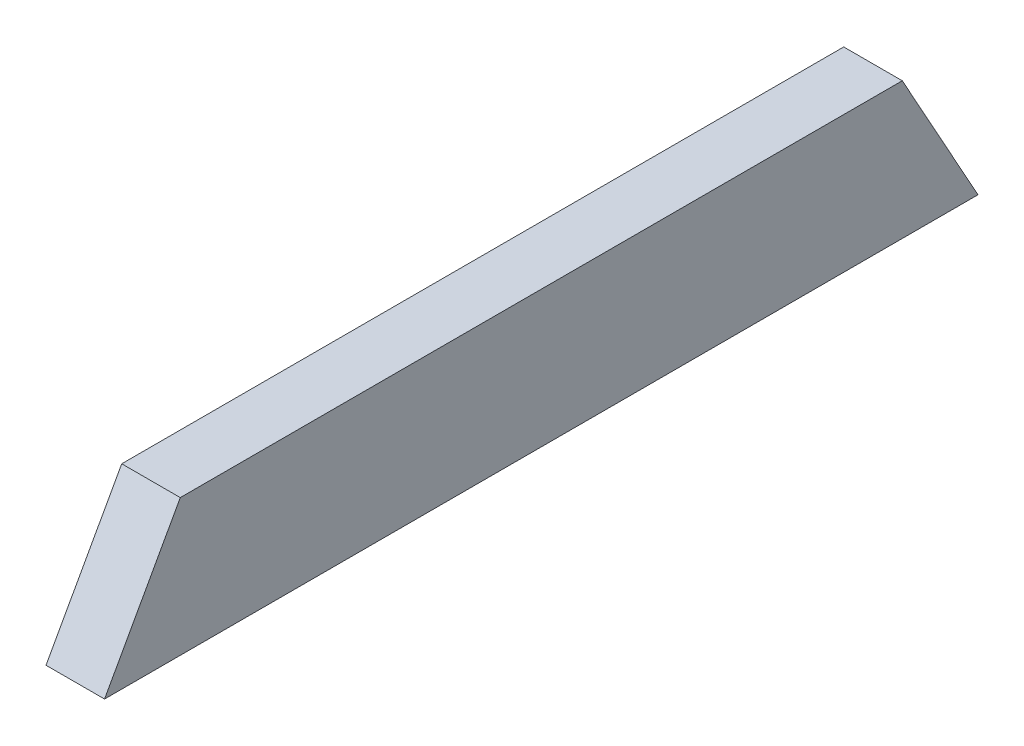
SolidWorks part; units mm, degrees
ref_plane "Front Plane" through (0, 0, 0) normal (0, 0, 1) x (1, 0, 0)
ref_plane "Top Plane" through (0, 0, 0) normal (0, 1, 0) x (1, 0, 0)
ref_plane "Right Plane" through (0, 0, 0) normal (1, 0, 0) x (0, 0, -1)
sketch "Sketch1" plane through (0, 0, 0) normal (0, 0, 1) x (1, 0, 0)
  line L1 (0, 0) -> (38.1, 0)
  line L2 (0, 0) -> (0, 88.9)
  line L3 (0, 88.9) -> (38.1, 88.9)
  line L4 (38.1, 0) -> (38.1, 88.9)
  dimension "D1" = 88.9
  dimension "D2" = 38.1
extrude "Boss-Extrude1" add sketch "Sketch1" along normal blind 568.3885
sketch "Sketch2" plane through (38.1, 0, 0) normal (1, 0, 0) x (0, 0, -1)
  line L0 (-519.1104, 88.9) -> (-568.3885, 0)
  line L1 (-568.3885, 88.9) -> (0, 88.9) construction
  line L2 (-568.3885, 0) -> (-568.3885, 88.9)
  line L3 (-568.3885, 88.9) -> (-519.1104, 88.9)
  line L4 (-49.2781, 88.9) -> (0, 0)
  line L5 (-49.2781, 88.9) -> (-519.1104, 88.9) construction
  line L6 (-49.2781, 88.9) -> (0, 88.9)
  line L7 (0, 88.9) -> (0, 0)
  dimension "D1" = 119
  dimension "D2" = 119
  dimension "D3" = 469.8324
extrude "Cut-Extrude1" cut sketch "Sketch2" against normal through all
